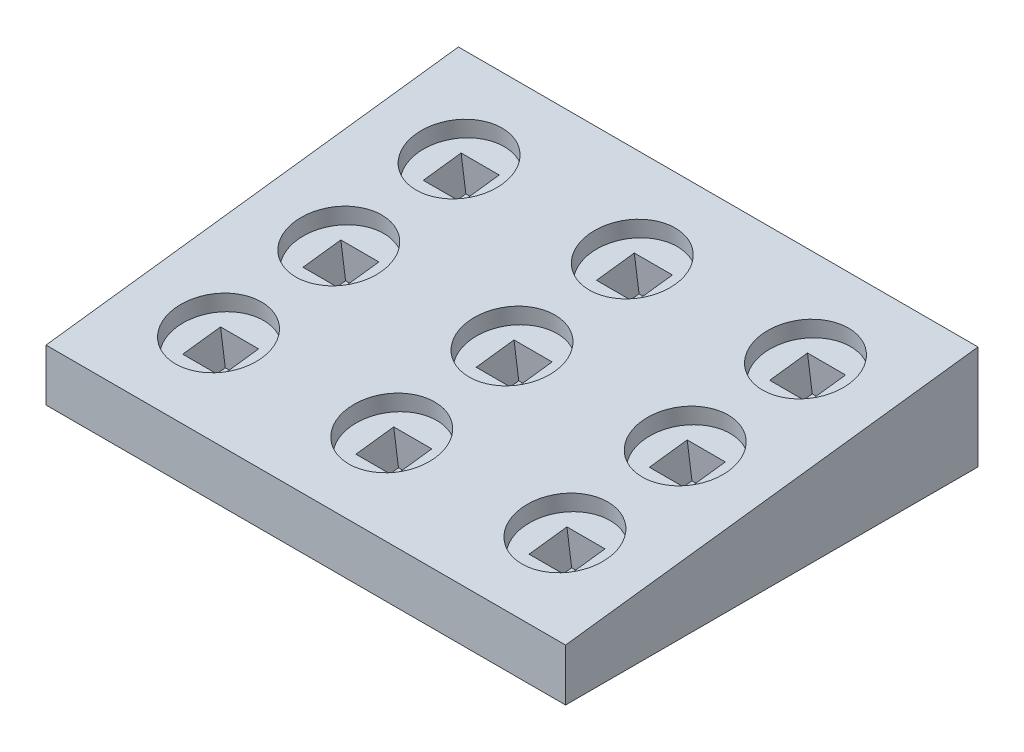
SolidWorks part; units mm, degrees
ref_plane "Front Plane" through (0, 0, 0) normal (0, 0, 1) x (1, 0, 0)
ref_plane "Top Plane" through (0, 0, 0) normal (0, 1, 0) x (1, 0, 0)
ref_plane "Right Plane" through (0, 0, 0) normal (1, 0, 0) x (0, 0, -1)
sketch "Sketch1" plane through (0, 0, 0) normal (1, 0, 0) x (0, 0, -1)
  line L0 (0, 0) -> (0, 38.1)
  line L1 (0, 38.1) -> (302.4094, 76.2)
  line L2 (302.4094, 76.2) -> (302.4094, 0)
  line L3 (302.4094, 0) -> (0, 0)
  dimension "D1" = 38.1
  dimension "D2" = 76.2
  dimension "D3" = 304.8
extrude "Boss-Extrude1" add sketch "Sketch1" along normal blind 381
ref_plane "Plane1" through (0, 40.0248, 5.0426) normal (0, 0.9922, 0.125) x (1, 0, 0)
sketch "Sketch2" plane through (0, 40.0248, 5.0426) normal (0, 0.9922, 0.125) x (1, 0, 0)
  line L0 (63.5, 246.0625) -> (0, 246.0625) construction
  line L2 (63.5, 246.0625) -> (190.5, 246.0625) construction
  line L3 (190.5, 246.0625) -> (317.5, 246.0625) construction
  line L4 (0, 309.5625) -> (0, 4.7625) construction
  line L5 (303.53, 232.0925) -> (331.47, 232.0925)
  line L6 (317.5, 246.0625) -> (317.5, 309.5625) construction
  line L7 (303.53, 232.0925) -> (303.53, 260.0325)
  line L8 (317.5, 246.0625) -> (317.5, 157.1625) construction
  line L9 (317.5, 157.1625) -> (317.5, 68.2625) construction
  line L10 (381, 309.5625) -> (0, 309.5625) construction
  line L11 (303.53, 260.0325) -> (331.47, 260.0325)
  line L12 (317.5, 246.0625) -> (381, 246.0625) construction
  line L13 (317.5, 68.2625) -> (317.5, 4.7625) construction
  line L14 (381, 309.5625) -> (381, 4.7625) construction
  line L15 (381, 4.7625) -> (0, 4.7625) construction
  line L16 (331.47, 232.0925) -> (331.47, 260.0325)
  line L17 (303.53, 232.0925) -> (331.47, 260.0325) construction
  line L18 (303.53, 260.0325) -> (331.47, 232.0925) construction
  line L19 (176.53, 143.1925) -> (204.47, 143.1925)
  line L20 (176.53, 143.1925) -> (176.53, 171.1325)
  line L21 (176.53, 171.1325) -> (204.47, 171.1325)
  line L22 (204.47, 143.1925) -> (204.47, 171.1325)
  line L23 (176.53, 143.1925) -> (204.47, 171.1325) construction
  line L24 (176.53, 171.1325) -> (204.47, 143.1925) construction
  line L25 (303.53, 54.2925) -> (331.47, 54.2925)
  line L26 (303.53, 54.2925) -> (303.53, 82.2325)
  line L27 (303.53, 82.2325) -> (331.47, 82.2325)
  line L28 (331.47, 54.2925) -> (331.47, 82.2325)
  line L29 (303.53, 54.2925) -> (331.47, 82.2325) construction
  line L30 (303.53, 82.2325) -> (331.47, 54.2925) construction
  line L31 (176.53, 54.2925) -> (204.47, 54.2925)
  line L32 (176.53, 54.2925) -> (176.53, 82.2325)
  line L33 (176.53, 82.2325) -> (204.47, 82.2325)
  line L34 (204.47, 54.2925) -> (204.47, 82.2325)
  line L35 (176.53, 54.2925) -> (204.47, 82.2325) construction
  line L36 (176.53, 82.2325) -> (204.47, 54.2925) construction
  line L37 (176.53, 232.0925) -> (204.47, 232.0925)
  line L38 (176.53, 232.0925) -> (176.53, 260.0325)
  line L39 (176.53, 260.0325) -> (204.47, 260.0325)
  line L40 (204.47, 232.0925) -> (204.47, 260.0325)
  line L41 (176.53, 232.0925) -> (204.47, 260.0325) construction
  line L42 (176.53, 260.0325) -> (204.47, 232.0925) construction
  line L43 (49.53, 143.1925) -> (77.47, 143.1925)
  line L44 (49.53, 143.1925) -> (49.53, 171.1325)
  line L45 (49.53, 171.1325) -> (77.47, 171.1325)
  line L46 (77.47, 143.1925) -> (77.47, 171.1325)
  line L47 (49.53, 143.1925) -> (77.47, 171.1325) construction
  line L48 (49.53, 171.1325) -> (77.47, 143.1925) construction
  line L49 (303.53, 143.1925) -> (331.47, 143.1925)
  line L50 (303.53, 143.1925) -> (303.53, 171.1325)
  line L51 (303.53, 171.1325) -> (331.47, 171.1325)
  line L52 (331.47, 143.1925) -> (331.47, 171.1325)
  line L53 (303.53, 143.1925) -> (331.47, 171.1325) construction
  line L54 (303.53, 171.1325) -> (331.47, 143.1925) construction
  line L55 (49.53, 54.2925) -> (77.47, 54.2925)
  line L56 (49.53, 54.2925) -> (49.53, 82.2325)
  line L57 (49.53, 82.2325) -> (77.47, 82.2325)
  line L58 (77.47, 54.2925) -> (77.47, 82.2325)
  line L59 (49.53, 54.2925) -> (77.47, 82.2325) construction
  line L60 (49.53, 82.2325) -> (77.47, 54.2925) construction
  line L61 (49.53, 232.0925) -> (77.47, 232.0925)
  line L62 (49.53, 232.0925) -> (49.53, 260.0325)
  line L63 (49.53, 260.0325) -> (77.47, 260.0325)
  line L64 (77.47, 232.0925) -> (77.47, 260.0325)
  line L65 (49.53, 232.0925) -> (77.47, 260.0325) construction
  line L66 (49.53, 260.0325) -> (77.47, 232.0925) construction
  circle A0 centre (63.5, 246.0625) radius 31.75
  circle A1 centre (190.5, 246.0625) radius 31.75
  circle A2 centre (317.5, 246.0625) radius 31.75
  circle A3 centre (63.5, 157.1625) radius 31.75
  circle A4 centre (63.5, 68.2625) radius 31.75
  circle A5 centre (190.5, 157.1625) radius 31.75
  circle A6 centre (190.5, 68.2625) radius 31.75
  circle A7 centre (317.5, 68.2625) radius 31.75
  circle A8 centre (317.5, 157.1625) radius 31.75
  point P18 (190.5, 157.1625)
  point P35 (317.5, 246.0625)
  point P43 (317.5, 68.2625)
  point P48 (190.5, 68.2625)
  point P53 (190.5, 246.0625)
  point P58 (63.5, 157.1625)
  point P63 (317.5, 157.1625)
  point P68 (63.5, 68.2625)
  point P73 (63.5, 246.0625)
  dimension "D1" = 63.5
  dimension "D2" = 63.5
  dimension "D3" = 27.94
extrude "Cut-Extrude2" cut sketch "Sketch2" against normal blind 15.24
extrude "Cut-Extrude3" cut sketch "Sketch2<3>" against normal blind 43.18 contours L55 L58 L57 L56 | L43 L46 L45 L44 | L61 L64 L63 L62 | L37 L40 L39 L38 | L19 L22 L21 L20 | L31 L34 L33 L32 | L49 L52 L51 L50 | L26 L27 L28 L25 | L5 L16 L11 L7 region at (190.5, 59.6701, -150.8872) region at (190.5, 48.5576, -62.6845) region at (190.5, 70.7826, -239.0899) region at (63.5, 59.6701, -150.8872) region at (317.5, 59.6701, -150.8872) region at (63.5, 48.5576, -62.6845) region at (63.5, 70.7826, -239.0899)
sketch "Sketch2<3>" plane through (0, 40.0248, 5.0426) normal (0, 0.9922, 0.125) x (1, 0, 0) same geometry as "Sketch2"
shell "Shell1" thickness 3.81 removed face at (190.5, 0, -151.2047)
